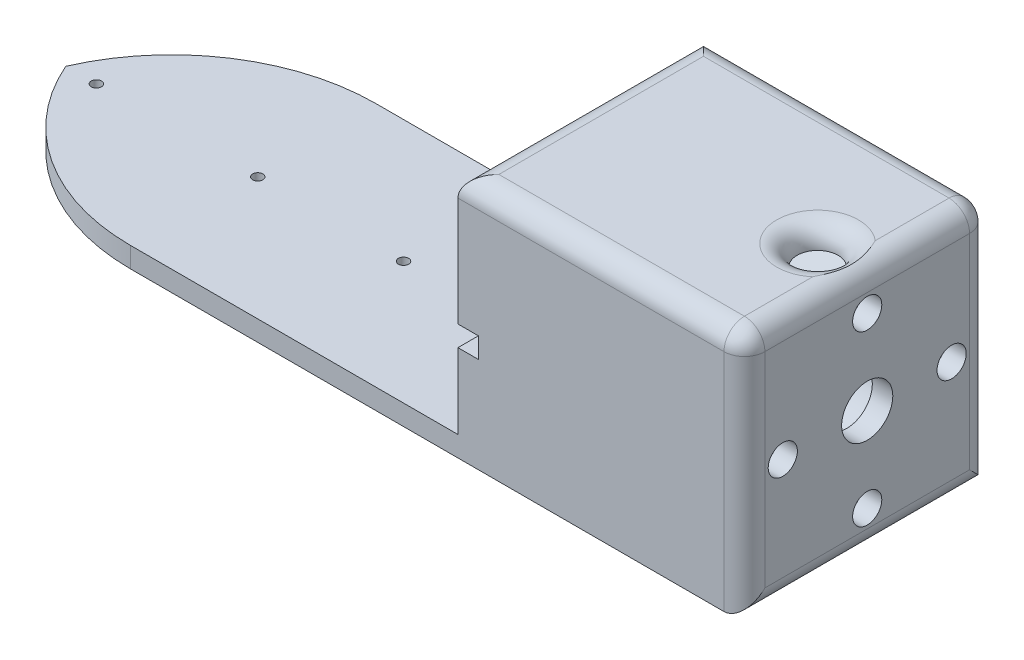
SolidWorks part; units mm, degrees
ref_plane "Front Plane" through (0, 0, 0) normal (0, 0, 1) x (1, 0, 0)
ref_plane "Top Plane" through (0, 0, 0) normal (0, 1, 0) x (1, 0, 0)
ref_plane "Right Plane" through (0, 0, 0) normal (1, 0, 0) x (0, 0, -1)
sketch "Sketch1" plane through (56.2103, 0, 0) normal (-1, 0, 0) x (0, 0, 1)
  line L0 (8.6202, 37.1553) -> (32.6202, 13.1553) construction
  line L1 (8.6202, 37.1553) -> (32.6202, 37.1553)
  line L2 (8.6202, 37.1553) -> (8.6202, 13.1553)
  line L3 (8.6202, 13.1553) -> (32.6202, 13.1553)
  line L4 (32.6202, 37.1553) -> (32.6202, 13.1553)
  line L5 (8.6202, 13.1553) -> (32.6202, 37.1553) construction
  circle A0 centre (20.6202, 25.1553) radius 2.5 construction
  point P19 (20.6202, 25.1553)
  dimension "D1" = 24
  dimension "D2" = 24
sketch "Sketch4" plane through (56.2103, 25.1553, 20.6202) normal (1, 0, 0) x (0, 0, -1)
  circle A0 centre (0, -8.25) radius 1.425 construction
  circle A3 centre (8.25, 0) radius 1.425 construction
  circle A4 centre (0, 8.25) radius 1.425 construction
  circle A5 centre (-8.25, 0) radius 1.425 construction
  circle A6 centre (0, 0) radius 2.5 construction
  circle A7 centre (0, -8.25) radius 1.425
  circle A8 centre (8.25, 0) radius 1.425
  circle A9 centre (0, 8.25) radius 1.425
  circle A10 centre (-8.25, 0) radius 1.425
  circle A11 centre (0, 0) radius 2.5
extrude "Boss-Extrude6" add sketch "Sketch1" along normal blind 28
shell "Shell6" thickness 2 removed face at (28.2103, 25.1553, 20.6202)
extrude "Cut-Extrude2" cut sketch "Sketch4" against normal blind 2
sketch "Sketch7" plane through (54.2103, 0, 0) normal (-1, 0, 0) x (0, 0, 1)
  line L0 (30.6202, 15.1553) -> (10.6202, 35.1553)
  line L1 (10.6202, 35.1553) -> (12.6202, 35.1553)
  line L2 (30.6202, 35.1553) -> (10.6202, 35.1553) construction
  line L3 (12.6202, 35.1553) -> (30.6202, 17.1553)
  line L4 (30.6202, 15.1553) -> (30.6202, 35.1553) construction
  line L5 (10.6202, 33.1553) -> (28.6202, 15.1553)
  line L6 (30.6202, 35.1553) -> (10.6202, 15.1553)
  line L7 (10.6202, 15.1553) -> (10.6202, 17.1553)
  line L8 (10.6202, 35.1553) -> (10.6202, 15.1553) construction
  line L9 (10.6202, 17.1553) -> (28.6202, 35.1553)
  line L10 (12.6202, 15.1553) -> (30.6202, 33.1553)
  line L11 (28.6202, 15.1553) -> (30.6202, 15.1553)
  line L12 (10.6202, 33.1553) -> (10.6202, 35.1553)
  line L13 (30.6202, 15.1553) -> (30.6202, 17.1553)
  line L14 (30.6202, 17.1553) -> (30.6202, 15.1553)
  line L15 (12.6202, 35.1553) -> (10.6202, 35.1553)
  line L16 (30.6202, 33.1553) -> (30.6202, 35.1553)
  line L17 (30.6202, 35.1553) -> (28.6202, 35.1553)
  line L18 (10.6202, 15.1553) -> (12.6202, 15.1553)
  line L19 (12.6202, 15.1553) -> (10.6202, 15.1553)
  circle A0 centre (20.6202, 25.1553) radius 4
  circle A1 centre (20.6202, 25.1553) radius 6
  line M6 (10.6202, 35.1553) -> (10.6202, 15.1553)
  line M7 (10.6202, 15.1553) -> (30.6202, 15.1553)
  line M8 (30.6202, 15.1553) -> (30.6202, 35.1553)
  line M9 (30.6202, 35.1553) -> (10.6202, 35.1553)
  line M11 (30.6202, 35.1553) -> (10.6202, 35.1553)
extrude "Boss-Extrude12" add sketch "Sketch7" along normal blind 15 contours A1 L0 L3 M8 | A1 L5 L0 M7 | A1 L6 L10 M7 | A1 L9 L6 M6 | A1 L0 L5 M6 | A1 L3 L0 M11 | A1 L6 L9 M9 | A1 L10 L6 M8 | L9 A1 L3 A0 | L6 A1 L9 A0 | L10 A1 L6 A0 | L3 A1 L10 A0 | L0 A1 L3 A0 | L5 A1 L0 A0 | L10 A1 L5 A0 | L6 A1 L10 A0 | L9 A1 L6 A0 | L5 A1 L9 A0 | L0 A1 L5 A0 | L3 A1 L0 A0 region at (54.2103, 17.8099, 26.9933) region at (54.2103, 18.7822, 27.9656) region at (54.2103, 21.1666, 23.6017) region at (54.2103, 22.1738, 24.6089) region at (54.2103, 20.2639, 20.6202) region at (54.2103, 25.1553, 25.5116) region at (54.2103, 17.8099, 14.2471) region at (54.2103, 31.5284, 27.9656) region at (54.2103, 21.1666, 17.6387) region at (54.2103, 18.7822, 13.2748) region at (54.2103, 28.1368, 24.6089) region at (54.2103, 32.5007, 26.9933) region at (54.2103, 22.1738, 16.6315) region at (54.2103, 29.144, 23.6017) region at (54.2103, 25.1553, 15.7288) region at (54.2103, 31.5284, 13.2748) region at (54.2103, 30.0467, 20.6202) region at (54.2103, 32.5007, 14.2471) region at (54.2103, 28.1368, 16.6315) region at (54.2103, 29.144, 17.6387)
sketch "Sketch5" plane through (0, 37.1553, 0) normal (0, 1, 0) x (1, 0, 0)
  circle A0 centre (51.6323, -20.8885) radius 2
extrude "Cut-Extrude4" cut sketch "Sketch5" against normal blind 10
sketch "Sketch8" plane through (28.2103, 0, 0) normal (-1, 0, 0) x (0, 0, 1)
  line L1 (8.6202, 13.1553) -> (32.6202, 13.1553)
  line L2 (8.6202, 13.1553) -> (8.6202, 15.1452)
  line L3 (8.6202, 15.1452) -> (32.6202, 15.1452)
  line L4 (32.6202, 13.1553) -> (32.6202, 15.1452)
extrude "Boss-Extrude13" add sketch "Sketch8" along normal blind 52
fillet "Fillet1" radius 20 2 edges at (-23.7897, 14.1503, 8.6202) (-23.7897, 14.1503, 32.6202)
sketch "Sketch12" plane through (0, 15.1452, 0) normal (0, 1, 0) x (1, 0, 0)
  circle A0 centre (-3.3778, -20.5973) radius 0.5
  circle A1 centre (-19.1296, -20.6178) radius 0.5
  circle A2 centre (10.888, -20.6178) radius 0.5011
  circle A3 centre (24.7546, -20.6178) radius 0.5
extrude "Cut-Extrude5" cut sketch "Sketch12" against normal blind 2
sketch "Sketch15" plane through (0, 0, 32.6202) normal (0, 0, 1) x (1, 0, 0)
  line L0 (28.2103, 15.1452) -> (28.2103, 37.1553) construction
  line L1 (28.2103, 22.4952) -> (30.2103, 22.4952)
  line L2 (28.2103, 22.4952) -> (28.2103, 24.4952)
  line L3 (28.2103, 24.4952) -> (30.2103, 24.4952)
  line L4 (30.2103, 22.4952) -> (30.2103, 24.4952)
  line L5 (-3.7897, 15.1452) -> (28.2103, 15.1452) construction
  dimension "D1" = 7.35
  dimension "D2" = 2
  dimension "D3" = 2
extrude "Cut-Extrude8" cut sketch "Sketch15" against normal through all
fillet "Fillet3" radius 2 8 edges at (42.2103, 37.1553, 32.6202) (28.2103, 37.1553, 20.6202) (42.2103, 37.1553, 8.6202) (56.2103, 37.1553, 20.6202) (51.6323, 37.1553, 22.8885) (56.2103, 13.1553, 20.6202) (56.2103, 25.1553, 8.6202) (56.2103, 25.1553, 32.6202)
